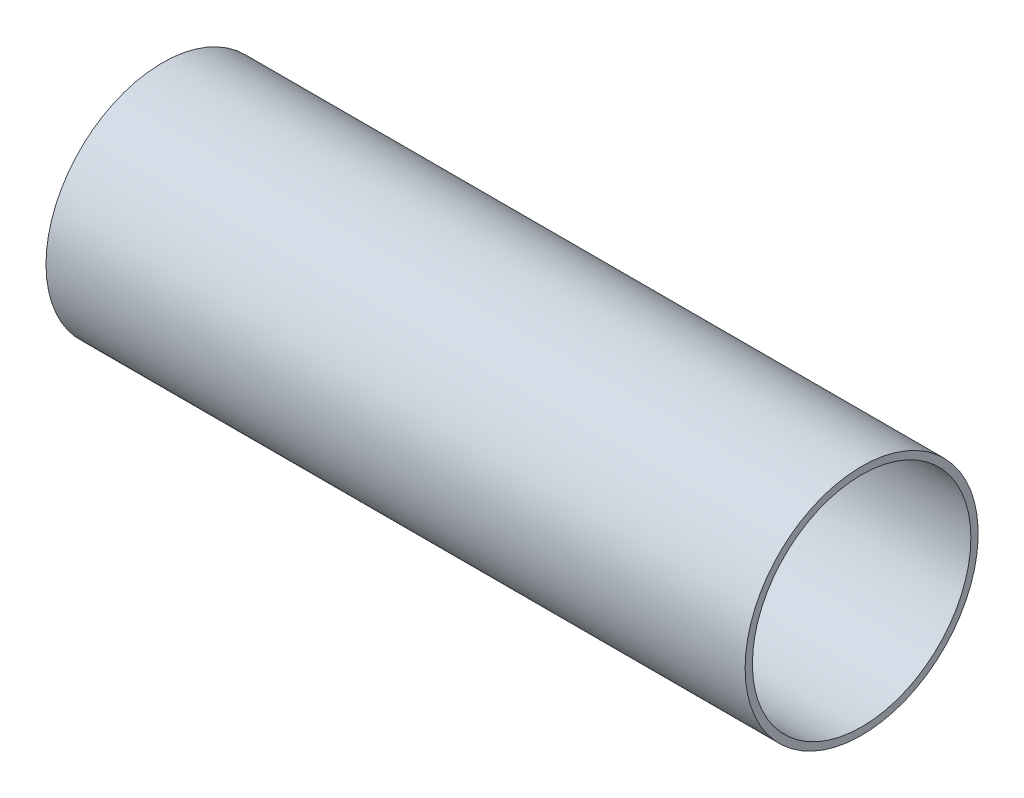
SolidWorks part; units mm, degrees
ref_plane "Front Plane" through (0, 0, 0) normal (0, 0, 1) x (1, 0, 0)
ref_plane "Top Plane" through (0, 0, 0) normal (0, 1, 0) x (1, 0, 0)
ref_plane "Right Plane" through (0, 0, 0) normal (1, 0, 0) x (0, 0, -1)
sketch "Sketch1" plane through (0, 0, 0) normal (1, 0, 0) x (0, 0, -1)
  circle A0 centre (0, 0) radius 203.2
extrude "Boss-Extrude2" add sketch "Sketch1" along normal blind 1219.2
sketch "Sketch2" plane through (0, 0, 0) normal (1, 0, 0) x (0, 0, -1)
  circle A0 centre (0, 0) radius 190.5
extrude "Cut-Extrude1" cut sketch "Sketch2" along normal blind 1219.2
